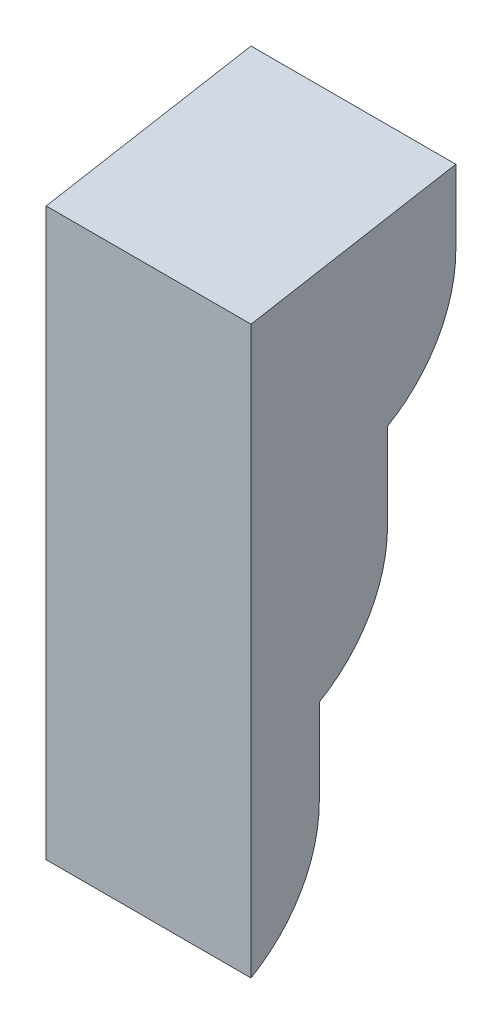
SolidWorks part; units mm, degrees
ref_plane "Front Plane" through (0, 0, 0) normal (0, 0, 1) x (1, 0, 0)
ref_plane "Top Plane" through (0, 0, 0) normal (0, 1, 0) x (1, 0, 0)
ref_plane "Right Plane" through (0, 0, 0) normal (1, 0, 0) x (0, 0, -1)
sketch "Sketch1" plane through (0, 0, 0) normal (1, 0, 0) x (0, 0, -1)
  line L0 (0, 45) -> (0, 0)
  line L1 (0, 0) -> (5, 0)
  line L2 (5, 0) -> (5, 15)
  line L8 (5, 15) -> (10, 15)
  line L9 (10, 15) -> (10, 30)
  line L10 (10, 30) -> (15, 30)
  line L11 (15, 30) -> (15, 45)
  line L13 (0, 45) -> (15, 45)
  dimension "D1" = 5
  dimension "D2" = 5
  dimension "D3" = 5
  dimension "D4" = 15
  dimension "D5" = 15
  dimension "D6" = 15
extrude "Boss-Extrude1" add sketch "Sketch1" along normal blind 7.5 and the other way blind 7.5
fillet "Fillet1" radius 10 1 edges at (0, 30, -15)
fillet "Fillet2" radius 10 2 edges at (0, 0, -5) (0, 15, -10)
sketch "Sketch2" plane through (7.5, 0, 0) normal (1, 0, 0) x (0, 0, -1)
  line L0 (-3.3944, 45) -> (20.01, 45)
  line L2 (20.01, 45) -> (-5.0853, 40.575)
  line L3 (15, 45) -> (0, 45) construction
  line L4 (-3.3944, 45) -> (-5.0853, 40.575)
  dimension "D1" = 10
extrude "Cut-Extrude1" cut sketch "Sketch2" against normal blind 24.5
